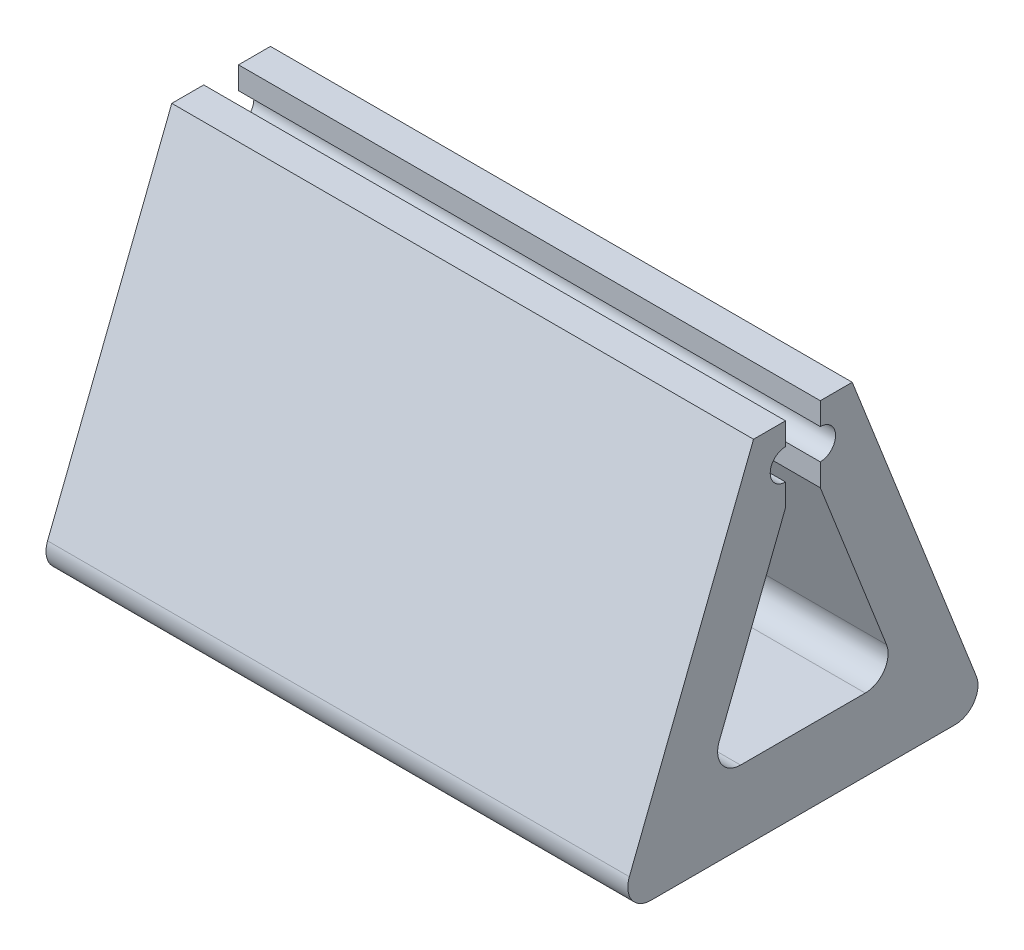
SolidWorks part; units mm, degrees
ref_plane "Front Plane" through (0, 0, 0) normal (0, 0, 1) x (1, 0, 0)
ref_plane "Top Plane" through (0, 0, 0) normal (0, 1, 0) x (1, 0, 0)
ref_plane "Right Plane" through (0, 0, 0) normal (1, 0, 0) x (0, 0, -1)
sketch "Sketch1" plane through (0, 0, 0) normal (1, 0, 0) x (0, 0, -1)
  line L0 (-0.456, 7.2216) -> (-0.456, 5.2461)
  line L1 (-1.633, 0) -> (1.633, 0)
  line L2 (0.456, 5.2461) -> (2.1916, 0.819)
  line L3 (0.456, 7.2216) -> (1.2927, 7.2216)
  line L4 (1.2927, 7.2216) -> (4.546, -1.0768)
  line L5 (3.9874, -1.8958) -> (-3.9874, -1.8958)
  line L6 (-4.546, -1.0768) -> (-1.2927, 7.2216)
  line L7 (-1.2927, 7.2216) -> (-0.456, 7.2216)
  line L8 (0, 0) -> (0, 50000) construction
  line L9 (-0.456, 5.2461) -> (-2.1916, 0.819)
  line L10 (0.456, 7.2216) -> (0.456, 5.2461)
  arc A0 (-2.1916, 0.819) -> (-1.633, 0) centre (-1.633, 0.6) ccw
  arc A1 (1.633, 0) -> (2.1916, 0.819) centre (1.633, 0.6) ccw
  arc A2 (-3.9874, -1.8958) -> (-4.546, -1.0768) centre (-3.9874, -1.2958) cw
  arc A3 (3.9874, -1.8958) -> (4.546, -1.0768) centre (3.9874, -1.2958) ccw
  arc A4 (-0.456, 5.8339) -> (-0.456, 6.6339) centre (-0.456, 6.2339) cw
  arc A5 (0.456, 5.8339) -> (0.456, 6.6339) centre (0.456, 6.2339) ccw
  point P26 (0, -1.8958)
  point P28 (13.8857, 5.155)
  point P29 (0, 0)
  dimension "D2" = 0.6
  dimension "D4" = 0.6
  dimension "D6" = 0.4
  dimension "D1" = 0.912
  dimension "D7" = 1.5
extrude "Boss-Extrude1" add sketch "Sketch1" along normal blind 15.24 contours L5 L8 L1 A0 L0 A4 L7 L6 A2 | L8 L5 A3 L4 L3 A5 A1 L1 region at (0, 6.9278, 0.5853)
